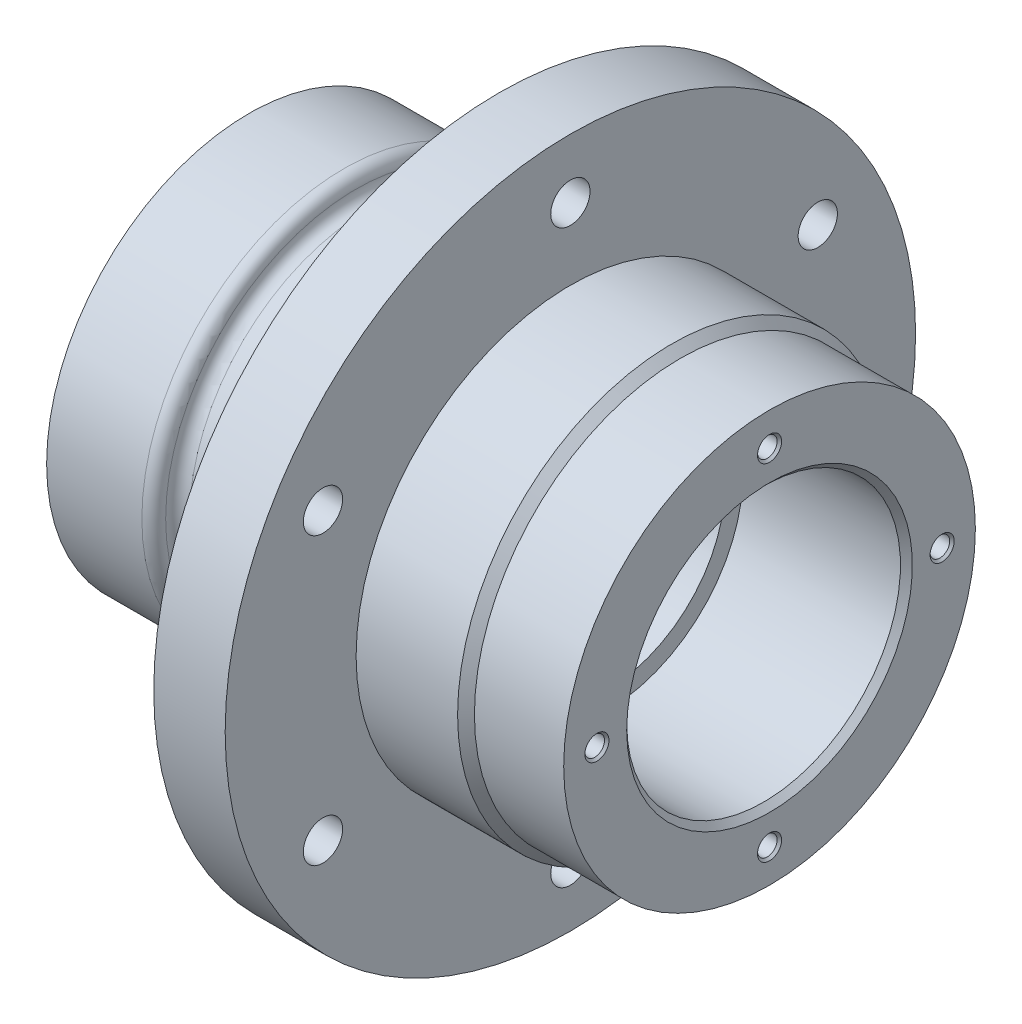
SolidWorks part; units mm, degrees
ref_plane "Front Plane" through (0, 0, 0) normal (0, 0, 1) x (1, 0, 0)
ref_plane "Top Plane" through (0, 0, 0) normal (0, 1, 0) x (1, 0, 0)
ref_plane "Right Plane" through (0, 0, 0) normal (1, 0, 0) x (0, 0, -1)
sketch "Sketch1" plane through (0, 0, 0) normal (0, 0, 1) x (1, 0, 0)
  line L0 (0, 0) -> (87.0891, 0) construction
  line L1 (0, 34) -> (0, 23)
  line L2 (0, 23) -> (15.5752, 23)
  line L3 (17.5752, 21) -> (17.5752, 20)
  line L4 (17.5752, 20) -> (28, 20)
  line L5 (28, 20) -> (28, 16)
  line L6 (28, 16) -> (48, 16)
  line L7 (48, 16) -> (48, 18)
  line L8 (50, 20) -> (60, 20)
  line L9 (60, 20) -> (60, 23)
  line L10 (60, 23) -> (86.4616, 23)
  line L11 (0, 34) -> (18, 34)
  line L12 (18, 34) -> (18, 30)
  line L13 (18, 30) -> (40, 30)
  line L14 (42, 32) -> (42, 58)
  line L15 (42, 58) -> (54, 58)
  line L16 (54, 58) -> (54, 36)
  line L17 (54, 36) -> (71.0474, 36)
  line L18 (71.0474, 36) -> (72.4616, 34.5858)
  line L19 (72.4616, 34.5858) -> (87.4616, 34.5858)
  line L20 (87.4616, 34.5858) -> (87.4616, 24)
  line L21 (87.4616, 24) -> (86.4616, 23)
  arc A0 (40, 30) -> (42, 32) centre (40, 32) ccw
  arc A1 (48, 18) -> (50, 20) centre (50, 18) cw
  arc A2 (15.5752, 23) -> (17.5752, 21) centre (15.5752, 21) cw
  point P5 (87.4616, 23)
  point P27 (42, 30)
  point P30 (48, 20)
  point P33 (17.5752, 23)
  dimension "D11" = 2
  dimension "D1" = 11
  dimension "D2" = 23
  dimension "D3" = 3
  dimension "D4" = 17.5752
  dimension "D5" = 28
  dimension "D6" = 4
  dimension "D7" = 20
  dimension "D8" = 4
  dimension "D9" = 12
  dimension "D10" = 3
  dimension "D12" = 18
  dimension "D13" = 4
  dimension "D14" = 24
  dimension "D15" = 28
  dimension "D16" = 12
  dimension "D17" = 22
  dimension "D18" = 135
  dimension "D19" = 2
  dimension "D20" = 15
revolve "Revolve1" add sketch "Sketch1" angle 360 about L0
sketch "Sketch2" plane through (42, 0, 0) normal (-1, 0, 0) x (0, 0, 1)
  circle A0 centre (0, 48) radius 7
  circle A1 centre (41.5692, 24) radius 7
  circle A2 centre (41.5692, -24) radius 7
  circle A3 centre (0, -48) radius 7
  circle A4 centre (-41.5692, -24) radius 7
  circle A5 centre (-41.5692, 24) radius 7
  point P15 (0, 0)
  dimension "D1" = 14
  dimension "D2" = 48
  dimension "D3" = 6
extrude "Boss-Extrude1" add sketch "Sketch2" along normal blind 2
fillet "Fillet1" radius 2 6 edges at (42, -24, -48.5692) (42, -48, -7) (42, -24, 34.5692) (42, 24, 34.5692) (42, 24, -48.5692) (42, 48, -7)
sketch "Sketch3" plane through (40, 0, 0) normal (-1, 0, 0) x (0, 0, 1)
  circle A0 centre (0, 48) radius 3.3
  circle A1 centre (41.5692, 24) radius 3.3
  circle A2 centre (41.5692, -24) radius 3.3
  circle A3 centre (0, -48) radius 3.3
  circle A4 centre (-41.5692, -24) radius 3.3
  circle A5 centre (-41.5692, 24) radius 3.3
  point P16 (0, 0)
  dimension "D1" = 6.6
  dimension "D2" = 6
extrude "Cut-Extrude1" cut sketch "Sketch3" against normal through all
sketch "Sketch4" plane through (87.4616, 0, 0) normal (1, 0, 0) x (0, 0, -1)
  point P0 (0, 29)
  point P5 (29, 0)
  point P6 (0, -29)
  point P7 (-29, 0)
  point P8 (0, 0)
  dimension "D1" = 29
  dimension "D2" = 4
hole_wizard "M4x0.7 Tapped Hole1" positions "3DSketch1" profile "Sketch5" tap size "M4x0.7" standard "ANSI Metric"
sketch3d "3DSketch1"
  point P0 (87.4616, 29, 0)
  point P3 (87.4616, 0, -29)
  point P6 (87.4616, -29, 0)
  point P9 (87.4616, 0, 29)
sketch "Sketch5" plane through (87.4616, 29, 0) normal (0, 1, 0) x (0, 0, -1)
  line L0 (0, 0) -> (0, 14.3914)
  line L1 (0, 14.3914) -> (1.65, 13.4)
  line L2 (1.65, 13.4) -> (1.65, 0.375)
  line L3 (1.65, 0.375) -> (2.025, 0)
  line L5 (2.025, 0) -> (0, 0)
  line L6 (-1.65, 0.375) -> (-2.025, 0) construction
  line L10 (0, 14.3914) -> (-1.65, 13.4) construction
  line L11 (0, -6.35) -> (0, 107.95) construction
  dimension "Tap Drill Dia." = 3.3
  dimension "Tap Drill Depth" = 13.4
  dimension "Near C'Sink Dia." = 4.05
  dimension "Near C'Sink Angle" = 90
  dimension "Drill Angle" = 118
cosmetic thread "Hole Thread1" parameters "D1"=11.3, "D2"=4
cosmetic thread "Hole Thread2" parameters "D1"=11.3, "D2"=4
cosmetic thread "Hole Thread3" parameters "D1"=11.3, "D2"=4
cosmetic thread "Hole Thread4" parameters "D1"=11.3, "D2"=4
ref_plane "Plane2" through (47.6916, 0, 0) normal (1, 0, 0) x (0, 0, -1)
sketch "Sketch6" plane through (0, 0, 0) normal (-1, 0, 0) x (0, 0, 1)
  point P0 (0, 28.956)
  point P5 (28.956, 0)
  point P6 (0, -28.956)
  point P7 (-28.956, 0)
  point P8 (0, 0)
  dimension "D1" = 28.956
  dimension "D2" = 4
hole_wizard "M4x0.7 Tapped Hole2" positions "3DSketch2" profile "Sketch7" tap size "M4x0.7" standard "ANSI Metric"
sketch3d "3DSketch2"
  point P0 (0, 28.956, 0)
  point P3 (0, 0, 28.956)
  point P6 (0, 0, -28.956)
  point P9 (0, -28.956, 0)
sketch "Sketch7" plane through (0, 28.956, 0) normal (0, 1, 0) x (0, 0, 1)
  line L0 (0, 0) -> (0, 14.4534)
  line L1 (0, 14.4534) -> (1.65, 13.462)
  line L2 (1.65, 13.462) -> (1.65, 0.375)
  line L3 (1.65, 0.375) -> (2.025, 0)
  line L5 (2.025, 0) -> (0, 0)
  line L6 (-1.65, 0.375) -> (-2.025, 0) construction
  line L10 (0, 14.4534) -> (-1.65, 13.462) construction
  line L11 (0, -6.35) -> (0, 107.95) construction
  dimension "Tap Drill Dia." = 3.3
  dimension "Tap Drill Depth" = 13.462
  dimension "Near C'Sink Dia." = 4.05
  dimension "Near C'Sink Angle" = 90
  dimension "Drill Angle" = 118
cosmetic thread "Hole Thread13" parameters "D1"=11.176, "D2"=4
cosmetic thread "Hole Thread14" parameters "D1"=11.176, "D2"=4
cosmetic thread "Hole Thread15" parameters "D1"=11.176, "D2"=4
cosmetic thread "Hole Thread16" parameters "D1"=11.176, "D2"=4
fillet "Fillet2" radius 2 2 edges at (18, 0, 34) (18, 0, 30)
